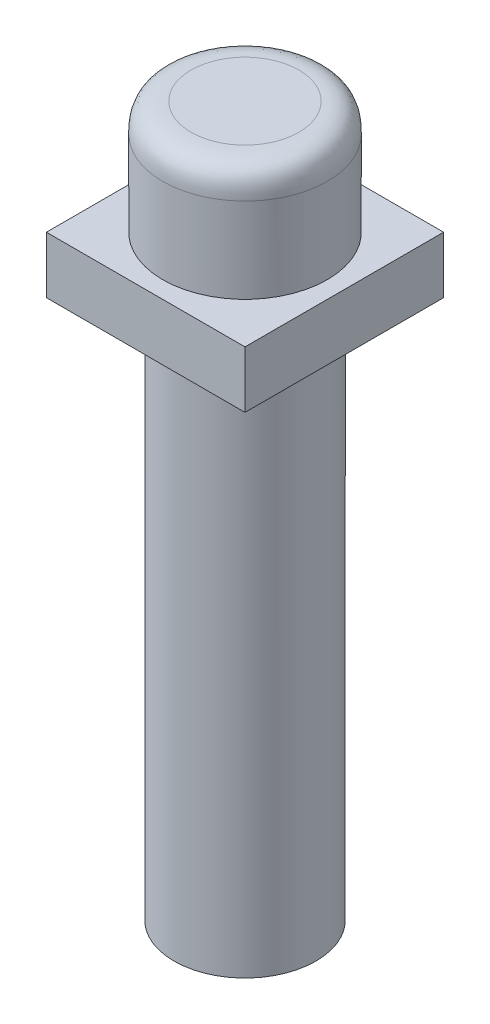
SolidWorks part; units mm, degrees
ref_plane "Front Plane" through (0, 0, 0) normal (0, 0, 1) x (1, 0, 0)
ref_plane "Top Plane" through (0, 0, 0) normal (0, 1, 0) x (1, 0, 0)
ref_plane "Right Plane" through (0, 0, 0) normal (1, 0, 0) x (0, 0, -1)
sketch "Sketch8" plane through (0, 0, 0) normal (0, 1, 0) x (1, 0, 0)
  line L1 (-3.5, 3.5) -> (3.5, 3.5)
  line L2 (-3.5, 3.5) -> (-3.5, -3.5)
  line L3 (-3.5, -3.5) -> (3.5, -3.5)
  line L4 (3.5, 3.5) -> (3.5, -3.5)
  line L5 (-3.5, 3.5) -> (3.5, -3.5) construction
  line L6 (-3.5, -3.5) -> (3.5, 3.5) construction
  point P0 (0, 0)
extrude "Boss-Extrude3" add sketch "Sketch8" along normal blind 2
sketch "Sketch9" plane through (0, 2, 0) normal (0, 1, 0) x (1, 0, 0)
  circle A0 centre (0, 0) radius 2.9
extrude "Boss-Extrude4" add sketch "Sketch9" along normal blind 4
sketch "Sketch10" plane through (0, 0, 0) normal (0, -1, 0) x (1, 0, 0)
  circle A0 centre (0, 0) radius 2.5
  circle A1 centre (0, 0) radius 1.25
extrude "Boss-Extrude5" add sketch "Sketch10" along normal blind 19
fillet "Fillet1" radius 1 1 edges at (0, 6, 2.9) curvature continuous yes second distance 1 first distance on face at (0, 6, 2.9)
